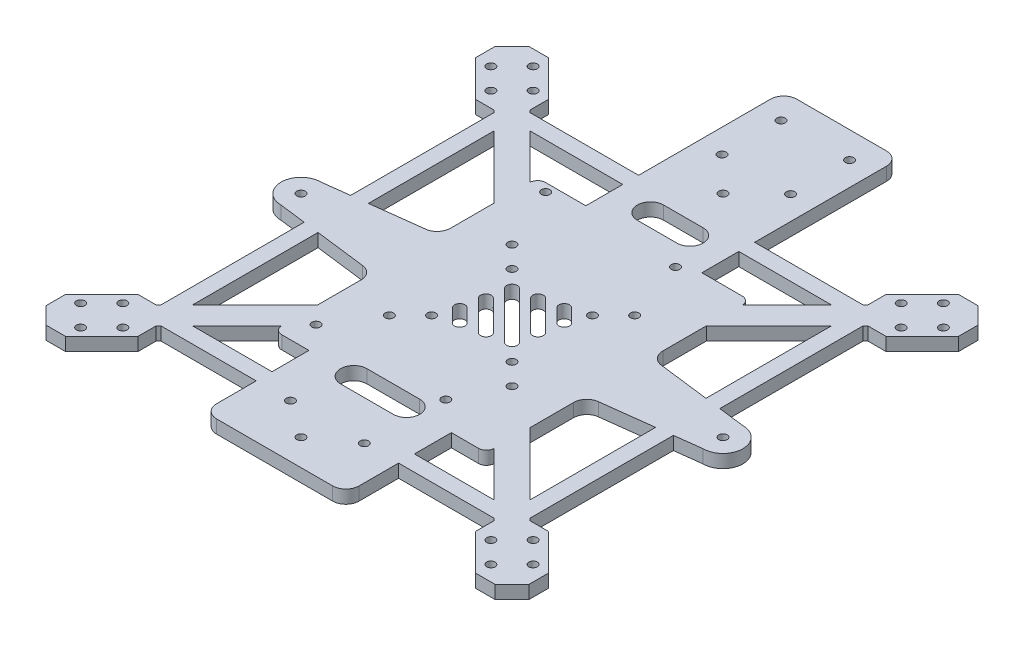
SolidWorks part; units mm, degrees
ref_plane "前视基准面" through (0, 0, 0) normal (0, 0, 1) x (1, 0, 0)
ref_plane "上视基准面" through (0, 0, 0) normal (0, 1, 0) x (1, 0, 0)
ref_plane "右视基准面" through (0, 0, 0) normal (1, 0, 0) x (0, 0, -1)
other "Configuration Table"
sketch "草图1" plane through (0, 0, 0) normal (0, 1, 0) x (1, 0, 0)
  line L0 (-40.28, 0) -> (40.28, 0) construction
  line L1 (-40.28, -50) -> (40.28, -50)
  line L2 (-40.28, -50) -> (-40.28, -16.9164)
  line L3 (-40.28, 50) -> (40.28, 50)
  line L4 (40.28, -50) -> (40.28, -16.9164)
  line L5 (-40.28, -50) -> (40.28, 50) construction
  line L6 (-40.28, 50) -> (40.28, -50) construction
  line L7 (0, -50) -> (0, 50) construction
  line L8 (-40.28, -50) -> (-40.28, -90) construction
  line L9 (-40.28, -90) -> (40.28, -90) construction
  line L10 (40.28, -90) -> (40.28, -50) construction
  line L11 (0, -50) -> (0, -90) construction
  line L12 (-40.28, -70) -> (40.28, -70) construction
  line L13 (-27, -90) -> (27, -90)
  line L14 (27, -90) -> (27, -50)
  line L15 (-27, -90) -> (-27, -50)
  line L16 (44.6626, 11.9547) -> (80, 7.5578)
  line L17 (44.6626, -11.9547) -> (80, -7.5578)
  line L18 (-44.6626, -11.9547) -> (-80, -7.5578)
  line L19 (-44.6626, 11.9547) -> (-80, 7.5578)
  line L20 (40.28, 16.9164) -> (40.28, 50)
  line L21 (-40.28, 16.9164) -> (-40.28, 50)
  circle A0 centre (-34.12, 46.89) radius 1.6
  circle A1 centre (15.09, 46.89) radius 1.6
  circle A2 centre (15.09, -40.19) radius 1.6
  circle A3 centre (-34.12, -40.19) radius 1.6
  circle A5 centre (-15.25, 15.25) radius 1.6
  circle A6 centre (15.25, 15.25) radius 1.6
  circle A7 centre (15.25, -15.25) radius 1.6
  circle A8 centre (-15.25, -15.25) radius 1.6
  circle A9 centre (14, -70) radius 1.6
  circle A10 centre (-14, -70) radius 1.6
  circle A11 centre (80, 0) radius 7.5 construction
  circle A12 centre (-80, 0) radius 7.5 construction
  circle A14 centre (80, 0) radius 1.6
  circle A16 centre (-80, 0) radius 1.6
  arc A17 (80, 7.5578) -> (80, -7.5578) centre (80, 0) cw
  arc A18 (-80, 7.5578) -> (-80, -7.5578) centre (-80, 0) ccw
  arc A19 (44.6626, 11.9547) -> (40.28, 16.9164) centre (45.28, 16.9164) cw
  arc A20 (44.6626, -11.9547) -> (40.28, -16.9164) centre (45.28, -16.9164) ccw
  arc A21 (-44.6626, -11.9547) -> (-40.28, -16.9164) centre (-45.28, -16.9164) cw
  arc A22 (-44.6626, 11.9547) -> (-40.28, 16.9164) centre (-45.28, 16.9164) ccw
  point P0 (0, 0)
  point P19 (0, 0)
  point P22 (0, 0)
  point P40 (0, -90)
  point P62 (40.28, 12.5)
  point P65 (40.28, -12.5)
  point P68 (-40.28, -12.5)
  point P71 (-40.28, 12.5)
  dimension "D3" = 3.2
  dimension "D10" = 3.2
  dimension "D11" = 30.5
  dimension "D12" = 30.5
  dimension "D14" = 3.2
  dimension "D18" = 15
  dimension "D21" = 3.2
  dimension "D19" = 160
  dimension "D23" = 5
  dimension "D1" = 80.56
  dimension "D2" = 100
  dimension "D4" = 6.16
  dimension "D5" = 3.11
  dimension "D8" = 49.21
  dimension "D9" = 87.08
  dimension "D13" = 40
  dimension "D15" = 28
  dimension "D16" = 54
  dimension "D17" = 25
  dimension "D6" = 2
  dimension "D7" = 2
extrude "凸台-拉伸1" add sketch "草图1" along normal blind 5 contours L15 L13 L14 L1 A9 A10 | L1 L4 L3 L2 A6 A5 A3 A2 A1 A0 A7 A8 region at (0.0313, 0, 0.011) region at (0, 0, 70)
sketch "草图6" plane through (0, 0, 0) normal (0, 1, 0) x (1, 0, 0)
  line L0 (0, 0) -> (50000, 0) construction
  line L1 (0, 0) -> (0, 50000) construction
  line L2 (-77.7817, 77.7817) -> (77.7817, 77.7817) construction
  line L3 (77.7817, 77.7817) -> (77.7817, -77.7817) construction
  line L4 (69.7817, 77.7817) -> (85.7817, 77.7817) construction
  line L5 (77.7817, 69.7817) -> (77.7817, 85.7817) construction
  line L6 (-77.7817, -77.7817) -> (77.7817, 77.7817) construction
  line L7 (77.7817, 91.5317) -> (64.0317, 77.7817)
  line L8 (91.5317, 77.7817) -> (77.7817, 64.0317)
  line L9 (-70.9067, 64.0317) -> (-40.28, 33.405)
  line L10 (-91.5317, -91.5317) -> (88.3498, 88.3498) construction
  line L11 (-87.5951, 87.5951) -> (77.7817, -77.7817) construction
  line L12 (40.28, -50) -> (40.28, 50)
  line L13 (40.28, 50) -> (-40.28, 50)
  line L14 (-40.28, 50) -> (-40.28, -50)
  line L15 (-40.28, -50) -> (40.28, -50)
  line L16 (-77.7817, 64.0317) -> (-70.9067, 64.0317)
  line L17 (-91.5317, 77.7817) -> (-77.7817, 64.0317)
  line L18 (-91.5317, 77.7817) -> (-91.5317, 85.1678)
  line L19 (-85.1678, 91.5317) -> (-91.5317, 85.1678)
  line L20 (-77.7817, 91.5317) -> (-85.1678, 91.5317)
  line L21 (77.7817, 91.5317) -> (85.1678, 91.5317)
  line L22 (91.5317, 77.7817) -> (91.5317, 85.1678)
  line L23 (-77.7817, 91.5317) -> (-64.0317, 77.7817)
  line L24 (-64.0317, 77.7817) -> (-64.0317, 70.9067)
  line L25 (72.1249, 83.4386) -> (83.4386, 72.1249) construction
  line L26 (77.7817, 64.0317) -> (70.9067, 64.0317)
  line L27 (64.0317, 77.7817) -> (64.0317, 70.9067)
  line L28 (77.7817, 64.0317) -> (70.9067, 64.0317)
  line L29 (64.0317, 77.7817) -> (64.0317, 70.9067)
  line L30 (64.0317, 70.9067) -> (40.28, 47.155)
  line L31 (70.9067, 64.0317) -> (40.28, 33.405)
  line L32 (85.1678, 91.5317) -> (91.5317, 85.1678)
  line L33 (-64.0317, 70.9067) -> (-40.28, 47.155)
  line L34 (-64.0317, -70.9067) -> (-40.28, -47.155)
  line L35 (-64.0317, -77.7817) -> (-64.0317, -70.9067)
  line L36 (-77.7817, -91.5317) -> (-64.0317, -77.7817)
  line L37 (-77.7817, -91.5317) -> (-85.1678, -91.5317)
  line L38 (-85.1678, -91.5317) -> (-91.5317, -85.1678)
  line L39 (-91.5317, -77.7817) -> (-91.5317, -85.1678)
  line L40 (-91.5317, -77.7817) -> (-77.7817, -64.0317)
  line L41 (-77.7817, -64.0317) -> (-70.9067, -64.0317)
  line L42 (-70.9067, -64.0317) -> (-40.28, -33.405)
  line L43 (70.9067, -64.0317) -> (40.28, -33.405)
  line L44 (77.7817, -64.0317) -> (70.9067, -64.0317)
  line L45 (91.5317, -77.7817) -> (77.7817, -64.0317)
  line L46 (91.5317, -77.7817) -> (91.5317, -85.1678)
  line L47 (85.1678, -91.5317) -> (91.5317, -85.1678)
  line L48 (77.7817, -91.5317) -> (85.1678, -91.5317)
  line L49 (77.7817, -91.5317) -> (64.0317, -77.7817)
  line L50 (64.0317, -77.7817) -> (64.0317, -70.9067)
  line L51 (64.0317, -70.9067) -> (40.28, -47.155)
  circle A0 centre (-77.7817, 77.7817) radius 65.9 construction
  circle A1 centre (77.7817, 77.7817) radius 65.9 construction
  circle A2 centre (-77.7817, -77.7817) radius 65.9 construction
  circle A3 centre (77.7817, -77.7817) radius 65.9 construction
  circle A4 centre (0, 0) radius 110 construction
  circle A5 centre (77.7817, 77.7817) radius 8 construction
  circle A6 centre (77.7817, 85.7817) radius 1.6
  circle A7 centre (85.7817, 77.7817) radius 1.6
  circle A8 centre (77.7817, 69.7817) radius 1.6
  circle A9 centre (69.7817, 77.7817) radius 1.6
  circle A10 centre (77.7817, 77.7817) radius 13.75 construction
  circle A11 centre (-77.7817, 85.7817) radius 1.6
  circle A12 centre (-85.7817, 77.7817) radius 1.6
  circle A13 centre (-69.7817, 77.7817) radius 1.6
  circle A14 centre (-77.7817, 69.7817) radius 1.6
  circle A15 centre (-77.7817, -69.7817) radius 1.6
  circle A16 centre (-69.7817, -77.7817) radius 1.6
  circle A17 centre (-85.7817, -77.7817) radius 1.6
  circle A18 centre (-77.7817, -85.7817) radius 1.6
  circle A19 centre (77.7817, -85.7817) radius 1.6
  circle A20 centre (85.7817, -77.7817) radius 1.6
  circle A21 centre (69.7817, -77.7817) radius 1.6
  circle A22 centre (77.7817, -69.7817) radius 1.6
  point P18 (77.7817, 77.7817)
  point P21 (77.7817, 77.7817)
  point P24 (0, 0)
  point P31 (77.7817, 77.7817)
  point P77 (77.7817, 77.7817)
  dimension "D1" = 3.2
  dimension "D2" = 3.2
  dimension "D3" = 3.2
  dimension "D4" = 3.2
  dimension "D5" = 3.2
  dimension "D6" = 3.2
  dimension "D7" = 3.2
  dimension "D8" = 3.2
  dimension "D9" = 3.2
  dimension "D10" = 3.2
  dimension "D11" = 3.2
  dimension "D12" = 3.2
  dimension "D13" = 3.2
  dimension "D14" = 3.2
  dimension "D15" = 3.2
  dimension "D16" = 3.2
extrude "凸台-拉伸3" add sketch "草图6" along normal blind 5 contours L33 L24 L23 L20 L19 L18 L17 L16 L9 L14 A13 A11 A12 A14 | L32 L21 L7 L27 L30 L12 L31 L26 L8 L22 A9 A8 A7 A6 | L51 L50 L49 L48 L47 L46 L45 L44 L43 L12 A21 A19 A20 A22 | L42 L41 L40 L39 L38 L37 L36 L35 L34 L14 A18 A17 A16 A15 region at (67.5211, 0, -67.3959) region at (67.5211, 0, 67.3959) region at (-67.5211, 0, -67.3959) region at (-67.5211, 0, 67.3959)
sketch "草图7" plane through (0, 0, 0) normal (0, 1, 0) x (1, 0, 0)
  line L0 (-8.8388, 8.8388) -> (8.8388, -8.8388) construction
  line L1 (-15.25, -15.25) -> (15.25, -15.25) construction
  line L2 (-15.25, -15.25) -> (-15.25, 15.25) construction
  line L3 (-15.25, 15.25) -> (15.25, 15.25) construction
  line L4 (15.25, -15.25) -> (15.25, 15.25) construction
  line L5 (-15.25, -15.25) -> (15.25, 15.25) construction
  line L6 (-15.25, 15.25) -> (15.25, -15.25) construction
  line L7 (-7.4246, 10.253) -> (10.253, -7.4246)
  line L8 (-10.253, 7.4246) -> (7.4246, -10.253)
  line L9 (-0.7071, 10.6066) -> (10.6066, -0.7071) construction
  line L10 (0.7071, 12.0208) -> (12.0208, 0.7071)
  line L11 (-2.1213, 9.1924) -> (9.1924, -2.1213)
  line L12 (7.4246, 12.3744) -> (12.3744, 7.4246) construction
  line L13 (8.8388, 13.7886) -> (13.7886, 8.8388)
  line L14 (6.0104, 10.9602) -> (10.9602, 6.0104)
  line L15 (-12.3744, -7.4246) -> (-7.4246, -12.3744) construction
  line L16 (-13.7886, -8.8388) -> (-8.8388, -13.7886)
  line L17 (-10.9602, -6.0104) -> (-6.0104, -10.9602)
  line L18 (-10.6066, 0.7071) -> (0.7071, -10.6066) construction
  line L19 (-12.0208, -0.7071) -> (-0.7071, -12.0208)
  line L20 (-9.1924, 2.1213) -> (2.1213, -9.1924)
  line L21 (0, -50) -> (0, 50) construction
  line L22 (-40.28, 50) -> (40.28, 50) construction
  line L23 (-27, -50) -> (27, -50) construction
  line L24 (-10, -50) -> (10, -50) construction
  line L25 (-10, -45) -> (10, -45)
  line L26 (-10, -55) -> (10, -55)
  arc A0 (-7.4246, 10.253) -> (-10.253, 7.4246) centre (-8.8388, 8.8388) ccw
  arc A1 (7.4246, -10.253) -> (10.253, -7.4246) centre (8.8388, -8.8388) ccw
  arc A2 (0.7071, 12.0208) -> (-2.1213, 9.1924) centre (-0.7071, 10.6066) ccw
  arc A3 (9.1924, -2.1213) -> (12.0208, 0.7071) centre (10.6066, -0.7071) ccw
  arc A4 (8.8388, 13.7886) -> (6.0104, 10.9602) centre (7.4246, 12.3744) ccw
  arc A5 (10.9602, 6.0104) -> (13.7886, 8.8388) centre (12.3744, 7.4246) ccw
  arc A6 (-13.7886, -8.8388) -> (-10.9602, -6.0104) centre (-12.3744, -7.4246) cw
  arc A7 (-6.0104, -10.9602) -> (-8.8388, -13.7886) centre (-7.4246, -12.3744) cw
  arc A8 (-12.0208, -0.7071) -> (-9.1924, 2.1213) centre (-10.6066, 0.7071) cw
  arc A9 (2.1213, -9.1924) -> (-0.7071, -12.0208) centre (0.7071, -10.6066) cw
  arc A10 (-10, -45) -> (-10, -55) centre (-10, -50) ccw
  arc A11 (10, -55) -> (10, -45) centre (10, -50) ccw
  circle A12 centre (0, -80) radius 1.6
  point P0 (0, 0)
  point P9 (0, 0)
  point P16 (4.9497, 4.9497)
  point P21 (9.8995, 9.8995)
  point P31 (-9.8995, -9.8995)
  point P38 (-4.9497, -4.9497)
  point P48 (0, 0)
  point P51 (0, -50)
  point P53 (0, -50)
  dimension "D3" = 4
  dimension "D7" = 2
  dimension "D9" = 5
  dimension "D11" = 3.2
  dimension "D1" = 4
  dimension "D2" = 25
  dimension "D4" = 3
  dimension "D5" = 16
  dimension "D6" = 7
  dimension "D8" = 3
  dimension "D10" = 20
  dimension "D12" = 80
extrude "切除-拉伸5" cut sketch "草图7" along normal through all contours A7 L17 A6 L16 | A9 L20 A8 L19 | L8 A1 L7 A0 | L11 A3 L10 A2 | L14 A5 L13 A4 | L26 A11 L25 A10 | A12 region at (0, 0, 0) region at (4.9497, 0, -4.9497) region at (9.8995, 0, -9.8995) region at (-9.8995, 0, 9.8995) region at (-4.9497, 0, 4.9497) region at (0, 0, 50) region at (0, 0, 80)
sketch "草图8" plane through (0, 0, 0) normal (0, 1, 0) x (1, 0, 0)
  line L0 (0, 0) -> (0, 87.5) construction
  line L1 (-40.28, 50) -> (40.28, 50) construction
  line L2 (-22, 125) -> (22, 125)
  line L3 (-22, 125) -> (-22, 50)
  line L4 (-22, 50) -> (22, 50)
  line L5 (22, 125) -> (22, 50)
  line L6 (-22, 125) -> (22, 50) construction
  line L7 (-22, 50) -> (22, 125) construction
  line L8 (13, 50) -> (13, 125) construction
  line L9 (-7.5, 60) -> (7.5, 60) construction
  line L10 (-7.5, 65) -> (7.5, 65)
  line L11 (-7.5, 55) -> (7.5, 55)
  circle A0 centre (13, 115) radius 1.6
  circle A1 centre (-13, 115) radius 1.6
  circle A2 centre (13, 92.63) radius 1.6
  circle A3 centre (-13, 92.63) radius 1.6
  arc A4 (-7.5, 65) -> (-7.5, 55) centre (-7.5, 60) ccw
  arc A5 (7.5, 55) -> (7.5, 65) centre (7.5, 60) ccw
  circle A6 centre (0, 80) radius 1.6
  point P21 (0, 60)
  dimension "D4" = 3.2
  dimension "D6" = 3.2
  dimension "D9" = 5
  dimension "D11" = 3.2
  dimension "D12" = 80
  dimension "D1" = 75
  dimension "D2" = 44
  dimension "D3" = 9
  dimension "D5" = 10
  dimension "D7" = 22.37
  dimension "D8" = 15
  dimension "D10" = 5
extrude "凸台-拉伸4" add sketch "草图8" along normal blind 5
fillet "圆角1" radius 5 4 edges at (-22, 2.5, -125) (22, 2.5, -125) (27, 2.5, 90) (-27, 2.5, 90)
fillet "圆角2" radius 3 4 edges at (-40.28, 2.5, 50) (40.28, 2.5, 50) (40.28, 2.5, -50) (-40.28, 2.5, -50)
sketch "草图9" plane through (0, 0, 0) normal (0, 1, 0) x (1, 0, 0)
  line L0 (64, 9.5486) -> (64, 57.125)
  line L1 (-57.125, -64) -> (-27, -64)
  line L2 (-64, -57.125) -> (-64, -9.5486)
  line L3 (-57.125, 64) -> (-22, 64)
  line L4 (64, -57.125) -> (64, -9.5486)
  line L5 (-64, -64) -> (64, 64) construction
  line L6 (-64, 64) -> (64, -64) construction
  line L7 (-63.125, -70) -> (-27, -70)
  line L8 (-70, -63.125) -> (-70, -8.8021)
  line L9 (-63.125, 70) -> (-22, 70)
  line L10 (70, -63.125) -> (70, -8.8021)
  line L11 (-70, -70) -> (70, 70) construction
  line L12 (-70, 70) -> (70, -70) construction
  line L13 (70, 8.8021) -> (70, 63.125)
  line L14 (22, 50) -> (22, 120) construction
  line L15 (22, 64) -> (22, 70)
  line L16 (22, 70) -> (63.125, 70)
  line L17 (22, 64) -> (57.125, 64)
  line L18 (-64, 9.5486) -> (-64, 57.125)
  line L19 (-70, 8.8021) -> (-70, 63.125)
  line L20 (27, -64) -> (57.125, -64)
  line L21 (27, -70) -> (63.125, -70)
  line L66 (-64.0317, -70.9067) -> (-40.28, -47.155)
  line L67 (-37.284, -50) -> (-27, -50)
  line L68 (-27, -50) -> (-27, -85)
  line L69 (-22, -90) -> (22, -90)
  line L70 (27, -85) -> (27, -50)
  line L71 (27, -50) -> (37.284, -50)
  line L72 (40.28, -47.155) -> (64.0317, -70.9067)
  line L73 (64.0317, -70.9067) -> (64.0317, -77.7817)
  line L74 (64.0317, -77.7817) -> (77.7817, -91.5317)
  line L75 (77.7817, -91.5317) -> (85.1678, -91.5317)
  line L76 (85.1678, -91.5317) -> (91.5317, -85.1678)
  line L77 (91.5317, -85.1678) -> (91.5317, -77.7817)
  line L78 (91.5317, -77.7817) -> (77.7817, -64.0317)
  line L79 (77.7817, -64.0317) -> (70.9067, -64.0317)
  line L80 (70.9067, -64.0317) -> (40.28, -33.405)
  line L81 (40.28, -33.405) -> (40.28, -16.9164)
  line L82 (44.6626, -11.9547) -> (80, -7.5578)
  line L83 (80, 7.5578) -> (44.6626, 11.9547)
  line L84 (40.28, 16.9164) -> (40.28, 33.405)
  line L85 (40.28, 33.405) -> (70.9067, 64.0317)
  line L86 (70.9067, 64.0317) -> (77.7817, 64.0317)
  line L87 (77.7817, 64.0317) -> (91.5317, 77.7817)
  line L88 (91.5317, 77.7817) -> (91.5317, 85.1678)
  line L89 (91.5317, 85.1678) -> (85.1678, 91.5317)
  line L90 (85.1678, 91.5317) -> (77.7817, 91.5317)
  line L91 (77.7817, 91.5317) -> (64.0317, 77.7817)
  line L92 (64.0317, 77.7817) -> (64.0317, 70.9067)
  line L93 (64.0317, 70.9067) -> (40.28, 47.155)
  line L94 (37.284, 50) -> (22, 50)
  line L95 (22, 50) -> (22, 120)
  line L96 (17, 125) -> (-17, 125)
  line L97 (-22, 120) -> (-22, 50)
  line L98 (-22, 50) -> (-37.284, 50)
  line L99 (-40.28, 47.155) -> (-64.0317, 70.9067)
  line L100 (-64.0317, 70.9067) -> (-64.0317, 77.7817)
  line L101 (-64.0317, 77.7817) -> (-77.7817, 91.5317)
  line L102 (-77.7817, 91.5317) -> (-85.1678, 91.5317)
  line L103 (-85.1678, 91.5317) -> (-91.5317, 85.1678)
  line L104 (-91.5317, 85.1678) -> (-91.5317, 77.7817)
  line L105 (-91.5317, 77.7817) -> (-77.7817, 64.0317)
  line L106 (-77.7817, 64.0317) -> (-70.9067, 64.0317)
  line L107 (-70.9067, 64.0317) -> (-40.28, 33.405)
  line L108 (-40.28, 33.405) -> (-40.28, 16.9164)
  line L109 (-44.6626, 11.9547) -> (-80, 7.5578)
  line L110 (-80, -7.5578) -> (-44.6626, -11.9547)
  line L111 (-40.28, -16.9164) -> (-40.28, -33.405)
  line L112 (-40.28, -33.405) -> (-70.9067, -64.0317)
  line L113 (-70.9067, -64.0317) -> (-77.7817, -64.0317)
  line L114 (-77.7817, -64.0317) -> (-91.5317, -77.7817)
  line L115 (-91.5317, -77.7817) -> (-91.5317, -85.1678)
  line L116 (-91.5317, -85.1678) -> (-85.1678, -91.5317)
  line L117 (-85.1678, -91.5317) -> (-77.7817, -91.5317)
  line L118 (-77.7817, -91.5317) -> (-64.0317, -77.7817)
  line L119 (-64.0317, -77.7817) -> (-64.0317, -70.9067)
  line L120 (-63.125, -70) -> (-57.125, -64)
  line L122 (-27, -64) -> (-27, -70)
  line L124 (27, -70) -> (27, -64)
  line L126 (57.125, -64) -> (63.125, -70)
  line L134 (70, -63.125) -> (64, -57.125)
  line L136 (64, -9.5486) -> (70, -8.8021)
  line L137 (70, 8.8021) -> (64, 9.5486)
  line L139 (64, 57.125) -> (70, 63.125)
  line L147 (63.125, 70) -> (57.125, 64)
  line L151 (-22, 70) -> (-22, 64)
  line L153 (-57.125, 64) -> (-63.125, 70)
  line L161 (-70, 63.125) -> (-64, 57.125)
  line L163 (-64, 9.5486) -> (-70, 8.8021)
  line L164 (-70, -8.8021) -> (-64, -9.5486)
  line L166 (-64, -57.125) -> (-70, -63.125)
  arc A14 (-40.28, -47.155) -> (-37.284, -50) centre (-37.284, -47) ccw
  arc A15 (-27, -85) -> (-22, -90) centre (-22, -85) ccw
  arc A16 (22, -90) -> (27, -85) centre (22, -85) ccw
  arc A17 (37.284, -50) -> (40.28, -47.155) centre (37.284, -47) ccw
  arc A18 (44.6626, -11.9547) -> (40.28, -16.9164) centre (45.28, -16.9164) ccw
  arc A19 (80, -7.5578) -> (80, 7.5578) centre (80, 0) ccw
  arc A20 (40.28, 16.9164) -> (44.6626, 11.9547) centre (45.28, 16.9164) ccw
  arc A21 (40.28, 47.155) -> (37.284, 50) centre (37.284, 47) ccw
  arc A22 (22, 120) -> (17, 125) centre (17, 120) ccw
  arc A23 (-17, 125) -> (-22, 120) centre (-17, 120) ccw
  arc A24 (-37.284, 50) -> (-40.28, 47.155) centre (-37.284, 47) ccw
  arc A25 (-44.6626, 11.9547) -> (-40.28, 16.9164) centre (-45.28, 16.9164) ccw
  arc A26 (-80, 7.5578) -> (-80, -7.5578) centre (-80, 0) ccw
  arc A27 (-40.28, -16.9164) -> (-44.6626, -11.9547) centre (-45.28, -16.9164) ccw
  point P0 (0, 0)
  point P6 (0, 0)
  dimension "D1" = 128
  dimension "D2" = 128
  dimension "D3" = 140
  dimension "D4" = 140
  dimension "D5" = 0
extrude "凸台-拉伸6" add sketch "草图9" along normal blind 5
sketch "草图10" plane through (0, 0, 0) normal (0, 1, 0) x (1, 0, 0)
  line L0 (-87.5578, 0) -> (87.5578, 0) construction
  line L1 (0, -125) -> (0, 125) construction
  line L2 (17, 125) -> (-17, 125) construction
  arc A0 (80, -7.5578) -> (80, 7.5578) centre (80, 0) ccw construction
  circle A1 centre (-23.25, 23.25) radius 1.6
  circle A2 centre (23.25, 23.25) radius 1.6
  circle A7 centre (-23.25, 23.25) radius 1.6
  circle A8 centre (23.25, 23.25) radius 1.6
  circle A9 centre (23.25, -23.25) radius 1.6
  circle A10 centre (-23.25, -23.25) radius 1.6
  point P3 (0, 0)
  point P7 (0, 0)
  point P13 (0, 0)
  dimension "D1" = 3.2
  dimension "D7" = 46.5
  dimension "D6" = 46.5
extrude "切除-拉伸10" cut sketch "草图10" along normal through all contours A1 | A2 | A9 | A10 region at (-23.25, 0, -23.25) region at (23.25, 0, -23.25) region at (23.25, 0, 23.25) region at (-23.25, 0, 23.25)
